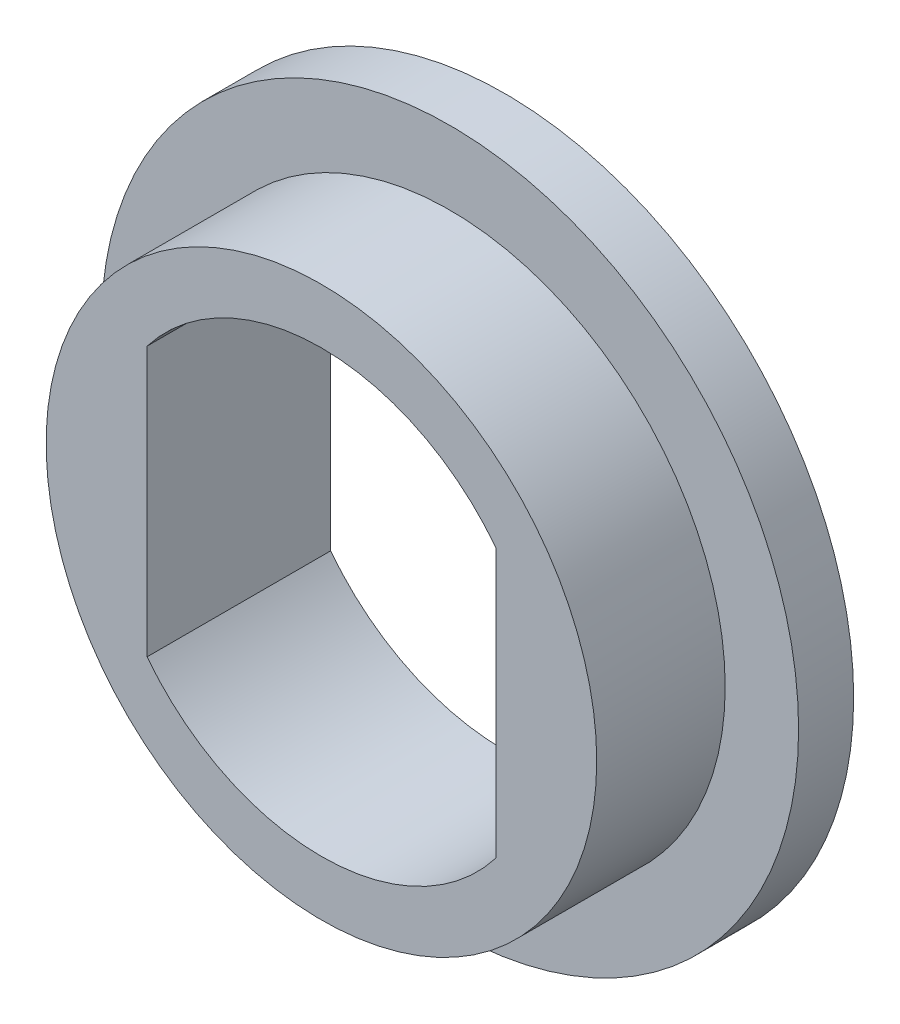
SolidWorks part; units mm, degrees
ref_plane "Plan de face" through (0, 0, 0) normal (0, 0, 1) x (1, 0, 0)
ref_plane "Plan de dessus" through (0, 0, 0) normal (0, 1, 0) x (1, 0, 0)
ref_plane "Plan de droite" through (0, 0, 0) normal (1, 0, 0) x (0, 0, -1)
sketch "Esquisse1" plane through (0, 0, 0) normal (0, 0, 1) x (1, 0, 0)
  line L0 (0, -15) -> (0, 15) construction
  line L1 (3, 10) -> (-3, 10)
  line L2 (-3, 10) -> (-3, 14.6969)
  line L3 (2, -9.8661) -> (-2, -9.8661)
  line L4 (-2, -9.8661) -> (-2, -14.8661)
  line L5 (-15, 0) -> (15, 0)
  line L6 (3, 10) -> (3, 14.6969)
  line L7 (2, -9.8661) -> (2, -14.8661)
  line L9 (9.5, -7.3314) -> (-9.5, -7.3314)
  line L10 (9.5, -7.3314) -> (9.5, 7.3314)
  line L11 (9.5, 7.3314) -> (-9.5, 7.3314)
  line L12 (-9.5, -7.3314) -> (-9.5, 7.3314)
  line L13 (9.5, -7.3314) -> (-9.5, 7.3314) construction
  line L14 (9.5, 7.3314) -> (-9.5, -7.3314) construction
  circle A0 centre (0, 0) radius 15
  circle A1 centre (0, 0) radius 12
  circle A2 centre (0, 0) radius 19
  point P16 (0, 10)
  point P17 (0, -9.8661)
  dimension "D1" = 30
  dimension "D2" = 24
  dimension "D8" = 38
  dimension "D3" = 3
  dimension "D4" = 5
  dimension "D5" = 2
  dimension "D6" = 5
  dimension "D7" = 19
extrude "Boss.-Extru.1" add sketch "Esquisse1" along normal blind 7 contours A1 L2 A0 L5 | A1 L5 A0 L4 | A1 L7 A0 L5 | A1 L4 A0 L7 | A1 L5 A0 L6 | A1 L6 A0 L2 | L12 A1 L5 | L5 A1 L12 | L5 A1 L10 | L10 A1 L5 region at (0, 13.3858, 0) region at (9.8152, 7.8382, 0) region at (-9.8152, 7.8382, 0) region at (10.5095, 2.792, 0) region at (-10.5095, 2.792, 0) region at (9.4273, -8.1257, 0) region at (10.5095, -2.792, 0) region at (-9.4273, -8.1257, 0) region at (-10.5095, -2.792, 0) region at (0, -13.4497, 0)
extrude "Boss.-Extru.2" add sketch "Esquisse1<4>" against normal blind 3 contours A2 A0 | A1 L5 A0 L6 | A1 L7 A0 L5 | A1 L4 A0 L7 | A1 L5 A0 L4 | A1 L2 A0 L5 | A1 L6 A0 L2 | L5 A1 L10 | L10 A1 L5 | L5 A1 L12 | L12 A1 L5 region at (0, 13.3858, 0) region at (9.8152, 7.8382, 0) region at (-9.8152, 7.8382, 0) region at (10.5095, 2.792, 0) region at (-10.5095, 2.792, 0) region at (9.4273, -8.1257, 0) region at (10.5095, -2.792, 0) region at (-9.4273, -8.1257, 0) region at (-10.5095, -2.792, 0) region at (0, -13.4497, 0) region at (-18.4626, 0, 0)
sketch "Esquisse1<4>" plane through (0, 0, 0) normal (0, 0, 1) x (1, 0, 0) same geometry as "Esquisse1"
